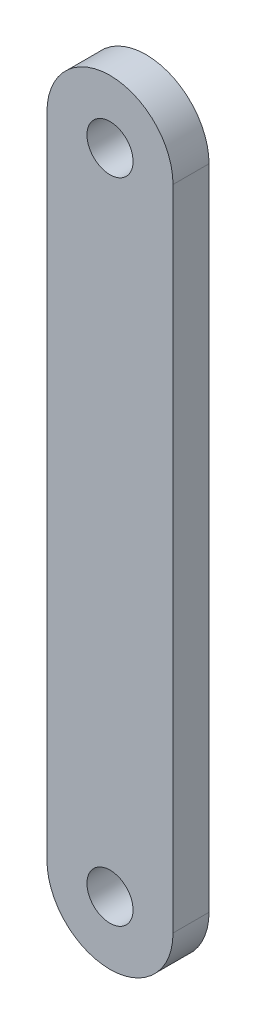
SolidWorks part; units mm, degrees
ref_plane "Front Plane" through (0, 0, 0) normal (0, 0, 1) x (1, 0, 0)
ref_plane "Top Plane" through (0, 0, 0) normal (0, 1, 0) x (1, 0, 0)
ref_plane "Right Plane" through (0, 0, 0) normal (1, 0, 0) x (0, 0, -1)
sketch "Sketch1" plane through (0, 0, 0) normal (0, 0, 1) x (1, 0, 0)
  line L0 (-8.89, 0) -> (-8.89, 91.44)
  line L1 (8.89, 91.44) -> (8.89, 0)
  line L2 (0, 0) -> (0, 91.44) construction
  arc A1 (8.89, 0) -> (-8.89, 0) centre (0, 0) cw
  circle A6 centre (0, 0) radius 3.2512
  arc A7 (8.89, 91.44) -> (-8.89, 91.44) centre (0, 91.44) ccw
  circle A8 centre (0, 91.44) radius 3.2512
  point P9 (0, 0)
  point P11 (0, 0)
  dimension "D1" = 8.89
  dimension "D2" = 91.44
  dimension "D4" = 6.5024
  dimension "D5" = 6.5024
extrude "Boss-Extrude1" add sketch "Sketch1" along normal blind 5.08
